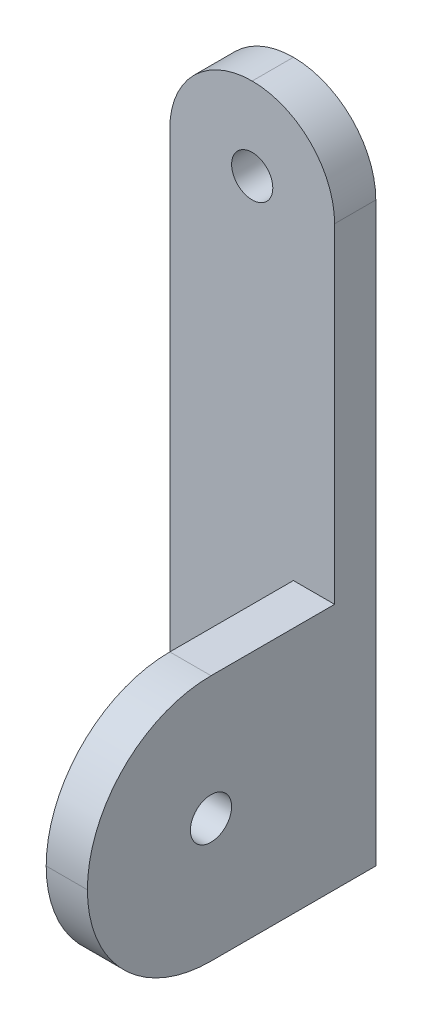
SolidWorks part; units mm, degrees
ref_plane "Plan de face" through (0, 0, 0) normal (0, 0, 1) x (1, 0, 0)
ref_plane "Plan de dessus" through (0, 0, 0) normal (0, 1, 0) x (1, 0, 0)
ref_plane "Plan de droite" through (0, 0, 0) normal (1, 0, 0) x (0, 0, -1)
sketch "Esquisse1" plane through (0, 0, 0) normal (0, 0, 1) x (1, 0, 0)
  line L1 (-17.3907, 12.9651) -> (2.6093, 12.9651)
  line L2 (-17.3907, 12.9651) -> (-17.3907, -67.0349)
  line L3 (-17.3907, -67.0349) -> (2.6093, -67.0349)
  line L4 (2.6093, 12.9651) -> (2.6093, -67.0349)
  dimension "D1" = 80
  dimension "D2" = 20
extrude "Boss.-Extru.1" add sketch "Esquisse1" along normal blind 5
sketch "Esquisse2" plane through (0, 0, 5) normal (0, 0, 1) x (1, 0, 0)
  line L0 (2.6093, 12.9651) -> (-17.3907, 12.9651) construction
  line L1 (-17.3907, 12.9651) -> (-17.3907, -67.0349) construction
  circle A0 centre (-7.3907, 2.9651) radius 2.5
  dimension "D1" = 5
  dimension "D2" = 10
  dimension "D3" = 10
extrude "Enlèv. mat.-Extru.1" cut sketch "Esquisse2" against normal blind 5
sketch "Esquisse3" plane through (0, 0, 5) normal (0, 0, 1) x (1, 0, 0)
  line L1 (2.6093, -67.0349) -> (-2.3907, -67.0349)
  line L2 (2.6093, -67.0349) -> (2.6093, -37.0349)
  line L3 (2.6093, -37.0349) -> (-2.3907, -37.0349)
  line L4 (-2.3907, -67.0349) -> (-2.3907, -37.0349)
  dimension "D1" = 30
  dimension "D2" = 5
extrude "Boss.-Extru.2" add sketch "Esquisse3" along normal blind 30
sketch "Esquisse4" plane through (2.6093, 0, 0) normal (1, 0, 0) x (0, 0, -1)
  line L0 (-35, -67.0349) -> (-35, -37.0349) construction
  line L1 (-35, -67.0349) -> (0, -67.0349) construction
  circle A0 centre (-20, -52.0349) radius 2.5
  dimension "D1" = 5
  dimension "D2" = 15
  dimension "D3" = 15
extrude "Enlèv. mat.-Extru.2" cut sketch "Esquisse4" against normal blind 30
fillet "Congé1" radius 15 2 edges at (0.1093, -67.0349, 35) (0.1093, -37.0349, 35)
fillet "Congé2" radius 10 3 edges at (-17.3907, -67.0349, 2.5) (2.6093, 12.9651, 2.5) (-17.3907, 12.9651, 2.5)
